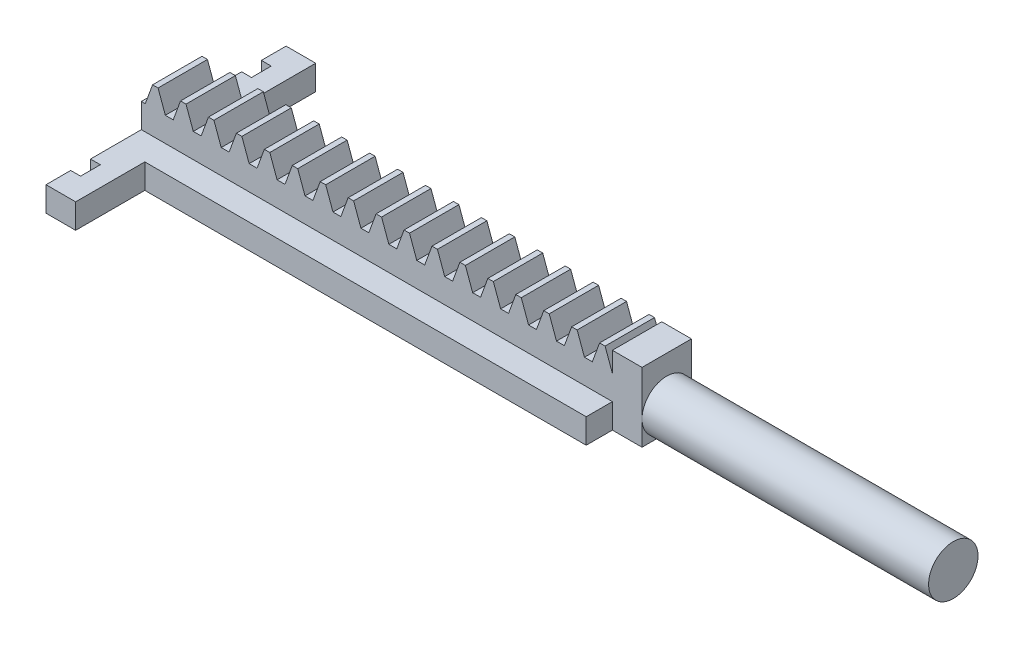
SolidWorks part; units mm, degrees
extrude "Blank" add sketch "BlankSke" against normal blind 5
sketch "BlankSke" plane through (0, 0, 0) normal (0, 0, 1) x (1, 0, 0)
  line L1 (0, 0) -> (47.667, 0)
  line L2 (0, 0) -> (0, 7)
  line L3 (0, 7) -> (47.667, 7)
  line L4 (47.667, 0) -> (47.667, 7)
  dimension "Length" = 47.667
  dimension "Blank_height" = 7
ref_plane "Plane1" through (0, 0, 0) normal (0, 0, 1) x (1, 0, 0)
ref_plane "Plane2" through (0, 0, 0) normal (0, 1, 0) x (1, 0, 0)
ref_plane "Plane3" through (0, 0, 0) normal (1, 0, 0) x (0, 0, -1)
other "Configuration Table"
sketch "HoldingSke" plane through (0, 0, 0) normal (0, 1, 0) x (1, 0, 0)
  line L0 (0, 0) -> (0.1546, 1.1003)
  line L1 (-15, 0) -> (100, 0) construction
  line L2 (0, 0) -> (-2.1039, 2.3779)
  line L3 (0, 0) -> (-11.863, 4.5341)
  line L4 (0, 0) -> (7.9495, 3.3743)
  line L5 (0, 0) -> (-23.7986, -8.8762)
  line L6 (0, 0) -> (-10.5278, -7.1032)
  line L9 (-71.009, 38.7566) -> (-14.6274, 59.2778)
  line L10 (-76.2, 3.2779) -> (-66.2, 3.2779)
  line L11 (0, 0) -> (-10, 0)
  line L12 (-76.2, 101.6) -> (-76.166, 101.6)
  line L13 (24.9733, 27.94) -> (52.9518, 28.4284)
  line L14 (24.9733, 27.94) -> (24.9743, 27.94)
  line L15 (24.9733, 27.94) -> (100.4006, 29.5858)
  circle A0 centre (0, 0) radius 19.05
  circle A1 centre (0, 0) radius 5
  circle A2 centre (0, 0) radius 12.7
  dimension "Num_teeth" = 23
  dimension "Width" = 10
sketch "TooCutSkeIll" plane through (0, 0, 0) normal (0, 0, 1) x (1, 0, 0)
  line L0 (0.2917, 6.9763) -> (-0.4535, 9.0237)
  line L1 (-0.2411, 8.875) -> (0.2411, 8.875)
  line L2 (0.4535, 9.0237) -> (-0.2917, 6.9763)
  line L3 (47.667, 7) -> (0, 7) construction
  line L4 (0, 0) -> (0, 64.897) construction
  line L5 (-13.208, 10) -> (12.954, 10) construction
  line L6 (0, 0) -> (47.667, 0) construction
  line L7 (0.8089, 10) -> (0.8089, 48.7463) construction
  line L8 (-0.8089, 10) -> (-0.8089, 48.7463) construction
  line L9 (-0.2578, 7) -> (-0.2578, 10.9254)
  line L10 (0.2578, 7) -> (0.2578, 10.9254)
  line L11 (0.2578, 10.9254) -> (-0.2578, 10.9254)
  arc A0 (0.2411, 8.875) -> (0.4535, 9.0237) centre (0.2411, 9.101) ccw
  arc A1 (-0.4535, 9.0237) -> (-0.2411, 8.875) centre (-0.2411, 9.101) ccw
  arc A2 (-0.2578, 7) -> (-0.2917, 6.9763) centre (-0.2578, 6.964) ccw
  arc A3 (0.2917, 6.9763) -> (0.2578, 7) centre (0.2578, 6.964) ccw
  dimension "Addendum_plus" = 0.9254
  dimension "Pressure_angle" = 20
  dimension "Gap_width" = 1.6177
  dimension "Dedendum" = 1.125
extrude "ToothCutIll" [suppressed] cut sketch "TooCutSkeIll" against normal through all
sketch "TooCutSkeSim" plane through (0, 0, 0) normal (0, 0, 1) x (1, 0, 0)
  line L0 (0.3994, 4.975) -> (-0.3994, 4.975)
  line L1 (1.1457, 7.0254) -> (0.3994, 4.975)
  line L2 (0, 17.4625) -> (0, 53.467) construction
  line L3 (1.1457, 7.0254) -> (-1.1457, 7.0254)
  line L6 (-1.1457, 7.0254) -> (-0.3994, 4.975)
  line L9 (-0.8089, 6.1) -> (0.8089, 6.1) construction
  line L10 (0, 0) -> (47.667, 0) construction
  line L11 (0.8089, 6.1) -> (0.8089, 53.467) construction
  line L12 (-0.8089, 6.1) -> (-0.8089, 53.467) construction
  dimension "Addendum_plus" = 0.9254
  dimension "Pitch_height" = 6.1
  dimension "Pressure_angle" = 20
  dimension "Gap_width" = 1.6177
  dimension "Dedendum" = 1.125
extrude "ToothCutSim" cut sketch "TooCutSkeSim" against normal through all
pattern_linear "TeethCuts" count 18 spacing 2.8274 along (1, 0, 0) of "ToothCutSim"
sketch "Sketch1" plane through (47.667, 0, 0) normal (1, 0, 0) x (0, 0, -1)
  line L0 (2.5, 4.975) -> (2.5, 0) construction
  line L1 (0, 4.975) -> (5, 4.975) construction
  line L2 (5, 0) -> (0, 0) construction
  line L3 (0, 2.4875) -> (5, 2.4875) construction
  line L4 (0, 0) -> (0, 4.975) construction
  line L5 (5, 0) -> (5, 4.975) construction
  circle A0 centre (2.5, 2.4875) radius 2.5
  dimension "D1" = 5
extrude "Boss-Extrude1" add sketch "Sketch1" along normal blind 32
sketch "Sketch2" plane through (0, 0, 0) normal (-1, 0, 0) x (0, 0, 1)
  line L0 (-2.5, 4.975) -> (-2.5, 0) construction
  line L1 (-7.6475, 2.5) -> (-5, 2.5)
  line L2 (-7.6475, 2.5) -> (-7.6475, 0)
  line L3 (-7.6475, 0) -> (-5, 0)
  line L4 (-5, 2.5) -> (-5, 0)
  line L5 (-7.6475, 2.5) -> (-5, 0) construction
  line L6 (-7.6475, 0) -> (-5, 2.5) construction
  line L7 (-5, 4.975) -> (0, 4.975) construction
  line L8 (-5, 0) -> (0, 0) construction
  line L9 (2.6475, 0) -> (0, 0)
  line L10 (0, 2.5) -> (0, 0)
  line L11 (2.6475, 2.5) -> (0, 2.5)
  line L12 (2.6475, 2.5) -> (2.6475, 0)
  point P0 (-6.3237, 1.25)
  dimension "D1" = 2.5
extrude "Boss-Extrude2" add sketch "Sketch2" against normal up to surface (47.667 mm away) up to face at (47.667, 0.6847, -4.4096)
sketch "Sketch3" plane through (47.667, 0, 0) normal (1, 0, 0) x (0, 0, -1)
  line L1 (0, 0) -> (5, 0)
  line L2 (0, 0) -> (0, 7)
  line L3 (0, 7) -> (5, 7)
  line L4 (5, 0) -> (5, 7)
  line L5 (0, 2.5) -> (0, 4.975) construction
  line L6 (5, 2.5) -> (5, 4.975) construction
  dimension "D1" = 7
extrude "Boss-Extrude3" add sketch "Sketch3" along normal blind 3
sketch "Sketch4" plane through (0, 0, -7.6475) normal (0, 0, -1) x (-1, 0, 0)
  line L0 (-47.667, 0) -> (0, 0) construction
  line L1 (-3, 2.5) -> (0, 2.5)
  line L2 (-3, 2.5) -> (-3, 0)
  line L3 (-3, 0) -> (0, 0)
  line L4 (0, 2.5) -> (0, 0)
  line L5 (-3, 2.5) -> (0, 0) construction
  line L6 (-3, 0) -> (0, 2.5) construction
  line L7 (-47.667, 2.5) -> (0, 2.5) construction
  line L8 (0, 2.5) -> (0, 0) construction
  point P0 (-1.5, 1.25)
  dimension "D1" = 3
extrude "Boss-Extrude4" add sketch "Sketch4" along normal blind 7
ref_plane "Plane4" through (0, 0, -2.5) normal (0, 0, -1) x (-1, 0, 0)
mirror "Mirror1" about plane through (0, 0, -2.5) normal (0, 0, -1) of "Boss-Extrude4"
sketch "Sketch5" plane through (0, 0, 0) normal (-1, 0, 0) x (0, 0, 1)
  line L0 (-14.6475, 0) -> (9.6475, 0) construction
  line L1 (-12.1475, 2.5) -> (-10.1475, 2.5)
  line L2 (-12.1475, 2.5) -> (-12.1475, 0)
  line L3 (-12.1475, 0) -> (-10.1475, 0)
  line L4 (-10.1475, 2.5) -> (-10.1475, 0)
  line L5 (-12.1475, 2.5) -> (-10.1475, 0) construction
  line L6 (-12.1475, 0) -> (-10.1475, 2.5) construction
  line L7 (-5, 2.5) -> (-14.6475, 2.5) construction
  line L8 (-14.6475, 0) -> (-14.6475, 2.5) construction
  point P0 (-11.1475, 1.25)
  dimension "D1" = 2.5
  dimension "D2" = 2
extrude "Cut-Extrude1" cut sketch "Sketch5" against normal blind 1
ref_plane "Plane5" through (0, 0, -2.5) normal (0, 0, -1) x (-1, 0, 0)
mirror "Mirror2" about plane through (0, 0, -2.5) normal (0, 0, -1) of "Cut-Extrude1"
equation "' \"Module@HoldingSke\" = 6.35"
equation "' \"Num_teeth@HoldingSke\" = 12"
equation "' \"Ap@HoldingSke\" =  20"
equation "' \"Ap@HoldingSke\" = 20"
equation "' \"Width@HoldingSke\" = 0.25 * 25.4"
equation "' \"Show_teeth@HoldingSke\" = 500"
equation "' \"Backlash@HoldingSke\" = 0.009 * 25.4"
equation "' \"Addendum_fac@HoldingSke\" = 1.0"
equation "' \"Dedendum_fac@HoldingSke\" = 1.25"
equation "' \"Dedendum_add@HoldingSke\" = 0.00005 * 25.4"
equation "' \"Clearance_fac@HoldingSke\" = 0.25"
equation "' \"Pitch_height@HoldingSke\" = 1 * 25.4"
equation "' \"Length@HoldingSke\" = 4.71 * 25.4"
equation "\"Pitch@HoldingSke\" = 1 / \"Module@HoldingSke\""
equation "\"MPH@HoldingSke\" = \"Dedendum_fac@HoldingSke\" / \"Pitch@HoldingSke\" + 2 * \"Dedendum_add@HoldingSke\" + 0.002 * 25.4"
equation "\"MPH@HoldingSke\" = ((sgn( \"MPH@HoldingSke\" - \"Pitch_height@HoldingSke\")+1)*( \"MPH@HoldingSke\" - \"Pitch_height@HoldingSke\"))/2 + \"Pitch_height@HoldingSke\""
equation "\"Pressure_angle@TooCutSkeIll\" = \"Ap@HoldingSke\""
equation "\"Addendum_plus@TooCutSkeIll\" =  \"Addendum_fac@HoldingSke\"  / \"Pitch@HoldingSke\" + 0.001 *25.4"
equation "\"Dedendum@TooCutSkeIll\" = \"Dedendum_fac@HoldingSke\"  / \"Pitch@HoldingSke\""
equation "\"Pitch_height@TooCutSkeIll\" =  \"MPH@HoldingSke\""
equation "\"Gap_width@TooCutSkeIll\" = 3.14159265 / 2 / \"Pitch@HoldingSke\" + 6 * \"Backlash@HoldingSke\""
equation "\"Pressure_angle@TooCutSkeSim\" = \"Ap@HoldingSke\""
equation "\"Addendum_plus@TooCutSkeSim\" =  \"Addendum_fac@HoldingSke\"  / \"Pitch@HoldingSke\" + 0.001 * 25.4"
equation "\"Dedendum@TooCutSkeSim\" = \"Dedendum_fac@HoldingSke\"  / \"Pitch@HoldingSke\""
equation "\"Gap_width@TooCutSkeSim\" = 3.14159265 / 2 / \"Pitch@HoldingSke\" + 6 * \"Backlash@HoldingSke\""
equation "\"Root_fillet@TooCutSkeIll\" = \"Clearance_fac@HoldingSke\" / \"Pitch@HoldingSke\" + \"Dedendum_add@HoldingSke\""
equation "\"Break_rad@TooCutSkeIll\" = 0.02 / \"Pitch@HoldingSke\" * 2"
equation "\"Linear_pitch@TeethCuts\" = 3.14159265 / \"Pitch@HoldingSke\""
equation "\"Num_teeth@HoldingSke\" = int( ( \"Length@HoldingSke\" + 0 ) / (3.14159265 / \"Pitch@HoldingSke\")) + 0.9999  + 1"
equation " \"Num_teeth@TeethCuts\" = ((sgn( \"Num_teeth@TeethCuts\" - \"Num_teeth@HoldingSke\" )-1)*( \"Num_teeth@TeethCuts\" - \"Num_teeth@HoldingSke\" ))/-2+ \"Num_teeth@HoldingSke\""
equation " \"Num_teeth@TeethCuts\" = ((sgn( \"Num_teeth@TeethCuts\" - 2.0)+1)*( \"Num_teeth@TeethCuts\" - 2.0))/2 +2.0"
